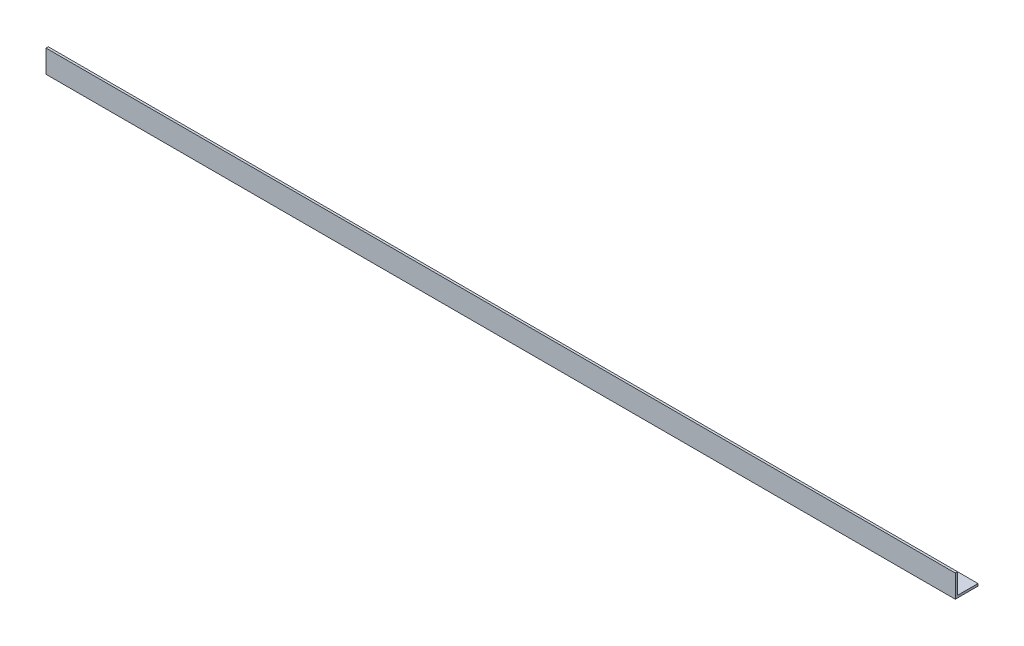
SolidWorks part; units mm, degrees
ref_plane "Спереди" through (0, 0, 0) normal (0, 0, 1) x (1, 0, 0)
ref_plane "Сверху" through (0, 0, 0) normal (0, 1, 0) x (1, 0, 0)
ref_plane "Справа" through (0, 0, 0) normal (1, 0, 0) x (0, 0, -1)
sketch "Эскиз1" plane through (0, 0, 0) normal (1, 0, 0) x (0, 0, -1)
  line L0 (0, 0) -> (0, 30)
  line L1 (0, 0) -> (30, 0)
extrude "Вытянуть-Тонкостенный1" add sketch "Эскиз1" along normal blind 1200 thin thin type one direction reverse wall 3
